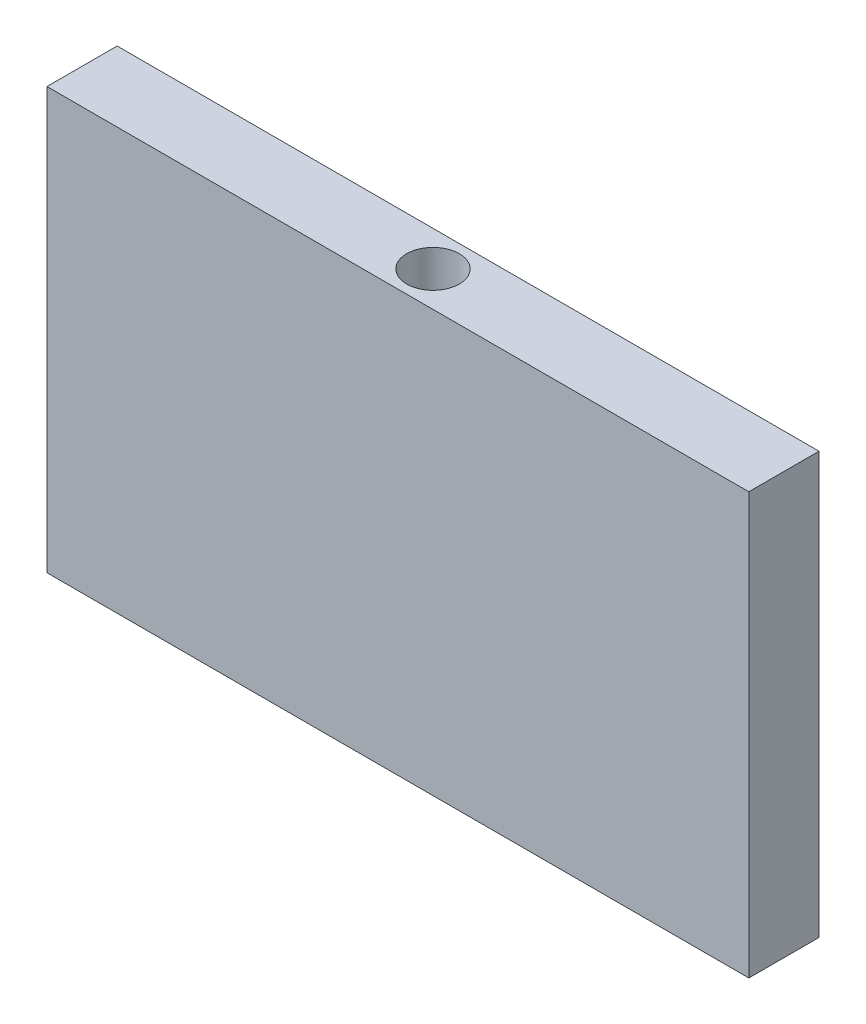
SolidWorks part; units mm, degrees
ref_plane "Front Plane" through (0, 0, 0) normal (0, 0, 1) x (1, 0, 0)
ref_plane "Top Plane" through (0, 0, 0) normal (0, 1, 0) x (1, 0, 0)
ref_plane "Right Plane" through (0, 0, 0) normal (1, 0, 0) x (0, 0, -1)
sketch "Sketch1" plane through (0, 0, 0) normal (0, 1, 0) x (1, 0, 0)
  line L1 (-20, 2) -> (20, 2)
  line L2 (-20, 2) -> (-20, -2)
  line L3 (-20, -2) -> (20, -2)
  line L4 (20, 2) -> (20, -2)
  line L5 (-20, 2) -> (20, -2) construction
  line L6 (-20, -2) -> (20, 2) construction
  point P0 (0, 0)
  dimension "D1" = 4
  dimension "D2" = 40
extrude "Boss-Extrude1" add sketch "Sketch1" along normal blind 24
sketch "Sketch2" plane through (0, 0, 0) normal (0, -1, 0) x (1, 0, 0)
  circle A0 centre (0, 0) radius 1.5
  dimension "D1" = 3
extrude "Cut-Extrude1" cut sketch "Sketch2" against normal blind 6
ref_plane "Plane1" through (0, 12, 0) normal (0, -1, 0) x (-1, 0, 0)
mirror "Mirror1" about plane through (0, 12, 0) normal (0, -1, 0) of "Cut-Extrude1"
